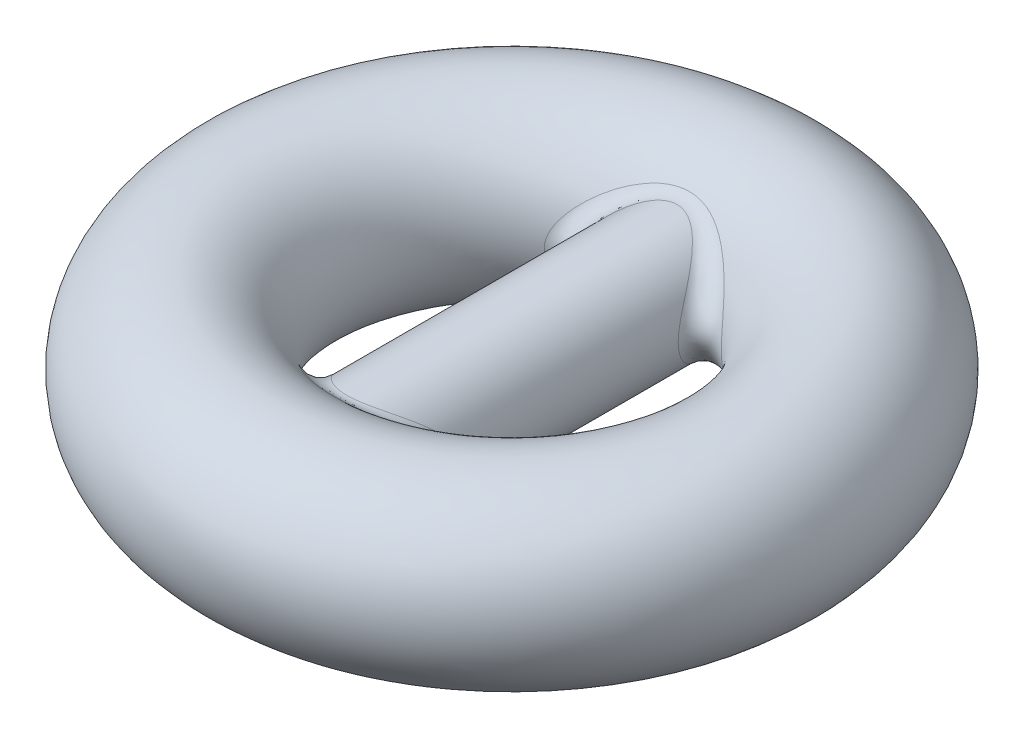
SolidWorks part; units mm, degrees
ref_plane "Front Plane" through (0, 0, 0) normal (0, 0, 1) x (1, 0, 0)
ref_plane "Top Plane" through (0, 0, 0) normal (0, 1, 0) x (1, 0, 0)
ref_plane "Right Plane" through (0, 0, 0) normal (1, 0, 0) x (0, 0, -1)
sketch "Sketch1" plane through (0, 0, 0) normal (0, 0, 1) x (1, 0, 0)
  circle A0 centre (0, 0) radius 10
  point P2 (0, 0)
  dimension "D1" = 20
extrude "Boss-Extrude1" add sketch "Sketch1" along normal blind 60
sketch "Sketch2" plane through (0, 0, 0) normal (1, 0, 0) x (0, 0, -1)
  line L0 (-30, 10) -> (-30, 25.6158) construction
  line L1 (0, 10) -> (-60, 10) construction
  circle A0 centre (10, 0) radius 15
  dimension "D2" = 30
  dimension "D1" = 10
revolve "Revolve1" add sketch "Sketch2" angle 360 about L0
fillet "Fillet1" radius 3 2 edges at (5.1646, 8.5631, 2.8016) (9.1108, 4.1224, 53.8999)
equation "\"dia_ring\"=30"
equation "\"D2@Sketch2\"=\"dia_ring\""
equation "\"center_length\"=60"
equation "\"D1@Boss-Extrude1\"=\"center_length\""
